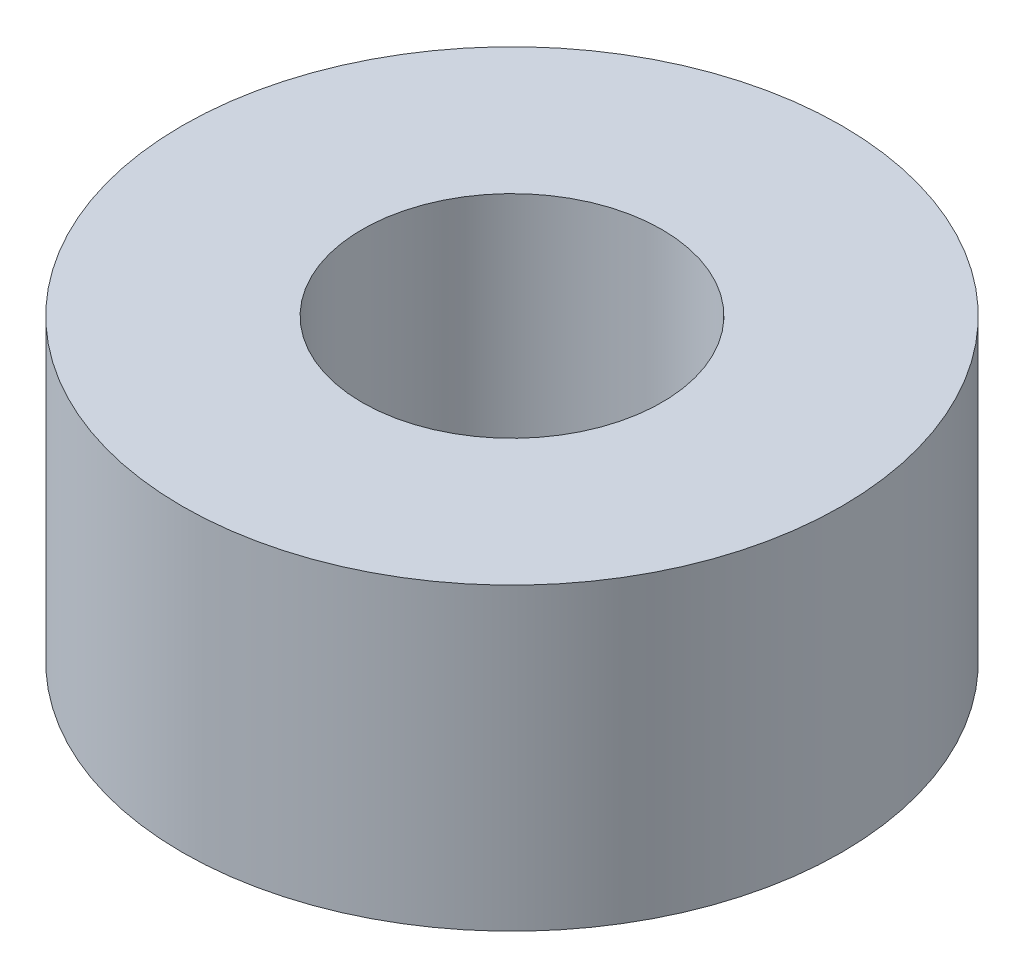
SolidWorks part; units mm, degrees
ref_plane "前视基准面" through (0, 0, 0) normal (0, 0, 1) x (1, 0, 0)
ref_plane "上视基准面" through (0, 0, 0) normal (0, 1, 0) x (1, 0, 0)
ref_plane "右视基准面" through (0, 0, 0) normal (1, 0, 0) x (0, 0, -1)
other "Configuration Table"
sketch "草图1" plane through (0, 0, 0) normal (0, 1, 0) x (1, 0, 0)
  circle A0 centre (0, 0) radius 5.5
  circle A1 centre (0, 0) radius 2.5
  dimension "D1" = 5
  dimension "D2" = 11
extrude "凸台-拉伸1" add sketch "草图1" along normal blind 5 contours A1 | A0 region at (0, 0, 0)
